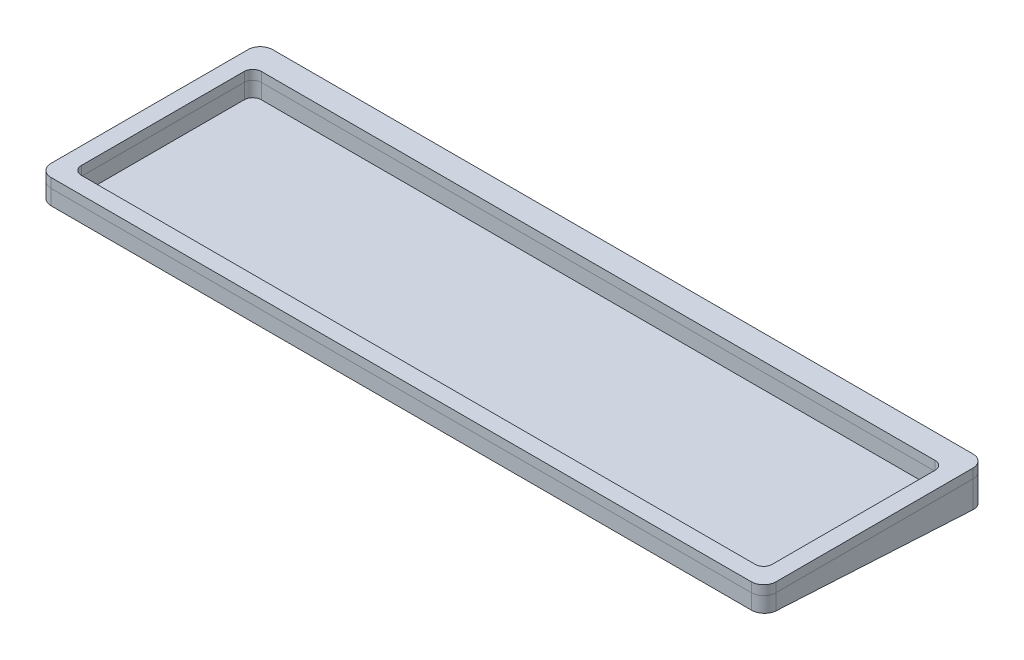
SolidWorks part; units mm, degrees
ref_plane "Front Plane" through (0, 0, 0) normal (0, 0, 1) x (1, 0, 0)
ref_plane "Top Plane" through (0, 0, 0) normal (0, 1, 0) x (1, 0, 0)
ref_plane "Right Plane" through (0, 0, 0) normal (1, 0, 0) x (0, 0, -1)
sketch "Sketch1" plane through (0, 0, 0) normal (0, 1, 0) x (1, 0, 0)
  line L0 (-179.825, 47.6224) -> (-179.825, 47.625)
  line L1 (-179.8217, 47.625) -> (179.825, 47.625)
  line L2 (-179.825, 47.6224) -> (-179.825, -47.625)
  line L3 (-179.825, -47.625) -> (179.825, -47.625)
  line L4 (179.825, 47.625) -> (179.825, -47.625)
  line L5 (-179.825, 47.625) -> (179.825, -47.625) construction
  line L6 (-179.825, -47.625) -> (179.825, 47.625) construction
  line L7 (-179.825, 47.625) -> (-179.8217, 47.625)
  circle A4 centre (157.075, 19.175) radius 1.1
  circle A5 centre (136.925, -16.775) radius 1.1
  circle A6 centre (-153.475, 33.725) radius 1.1
  circle A7 centre (17.925, 22.275) radius 1.1
  circle A8 centre (17.875, -35.075) radius 1.1
  circle A9 centre (-130.375, -35.725) radius 1.1
  point P0 (0, 0)
  dimension "D4" = 2.2
  dimension "D7" = 2.2
  dimension "D8" = 2.2
  dimension "D9" = 2.2
  dimension "D10" = 2.2
  dimension "D11" = 2.2
  dimension "D1" = 359.65
  dimension "D2" = 95.25
  dimension "D5" = 22.75
  dimension "D6" = 28.45
  dimension "D12" = 42.9
  dimension "D13" = 30.85
  dimension "D14" = 25.35
  dimension "D15" = 161.9
  dimension "D16" = 12.55
  dimension "D17" = 161.95
  dimension "D18" = 11.9
  dimension "D19" = 49.45
  dimension "D20" = 13.9
  dimension "D21" = 26.35
sketch "Sketch2" plane through (0, 0, 0) normal (0, 1, 0) x (1, 0, 0)
  line L0 (-188.825, 54.625) -> (-188.825, 60.625)
  line L1 (-188.825, 60.625) -> (-182.825, 60.625)
  line L3 (-188.825, 60.625) -> (-191.825, 60.625)
  line L4 (-182.825, 46.625) -> (-182.825, -46.625)
  line L5 (-178.825, -47.625) -> (178.825, -47.625)
  line L6 (182.825, 46.625) -> (182.825, -46.625)
  line L7 (-178.825, 47.625) -> (178.825, 47.625)
  line L8 (-182.825, 46.625) -> (-182.825, 47.625)
  line L9 (-182.825, 60.625) -> (188.825, 60.625)
  line L10 (-188.825, 54.625) -> (-188.825, -56.625)
  line L11 (-188.825, -56.625) -> (188.825, -56.625)
  line L12 (188.825, 60.625) -> (188.825, -56.625)
  line L13 (-182.825, 47.625) -> (-178.825, 47.625)
  line L14 (-182.825, -46.625) -> (-182.825, -47.625)
  line L15 (-182.825, -47.625) -> (-178.825, -47.625)
  line L16 (178.825, -47.625) -> (182.825, -47.625)
  line L17 (182.825, -47.625) -> (182.825, -46.625)
  line L18 (178.825, 47.625) -> (182.825, 47.625)
  line L19 (182.825, 47.625) -> (182.825, 46.625)
  line L20 (-188.825, 60.625) -> (-188.825, -56.625)
  line L21 (-188.825, -56.625) -> (-191.825, -56.625)
  line L22 (-191.825, 60.625) -> (-191.825, -56.625)
  line L23 (188.825, 60.625) -> (191.825, 60.625)
  line L24 (188.825, 60.625) -> (188.825, -56.625)
  line L25 (188.825, -56.625) -> (191.825, -56.625)
  line L26 (191.825, 60.625) -> (191.825, -56.625)
  circle A0 centre (157.075, 19.175) radius 1.1 construction
  circle A1 centre (136.925, -16.775) radius 1.1 construction
  circle A2 centre (17.875, -35.075) radius 1.1 construction
  circle A3 centre (17.925, 22.275) radius 1.1 construction
  circle A4 centre (-153.475, 33.725) radius 1.1 construction
  circle A5 centre (-130.375, -35.725) radius 1.1 construction
  circle A10 centre (157.075, 19.175) radius 1.1
  circle A11 centre (136.925, -16.775) radius 1.1
  circle A12 centre (17.875, -35.075) radius 1.1
  circle A13 centre (17.925, 22.275) radius 1.1
  circle A14 centre (-153.475, 33.725) radius 1.1
  circle A15 centre (-130.375, -35.725) radius 1.1
  point P30 (0, 0)
  dimension "D5" = 3
  dimension "D6" = 3
  dimension "D1" = 13
  dimension "D2" = 9
  dimension "D3" = 6
  dimension "D4" = 6
extrude "Boss-Extrude1" add sketch "Sketch2" along normal blind 13 contours L10 L11 L12 L9 L18 L19 L6 L17 L16 L5 L15 L14 L4 L8 L13 L7 | L20 L3 L22 L21 | L24 L23 L26 L25 region at (-184.8707, 0, -57.625)
sketch "Sketch4" plane through (0, 0, 0) normal (0, -1, 0) x (1, 0, 0)
  line L1 (-191.825, -60.625) -> (191.825, -60.625) construction
  line L3 (-191.825, 56.625) -> (191.825, 56.625) construction
  line L4 (-182.825, 47.625) -> (-182.825, -47.625)
  line L5 (182.825, 47.625) -> (-182.825, 47.625)
  line L6 (182.825, -47.625) -> (182.825, 47.625)
  line L7 (-182.825, -47.625) -> (182.825, -47.625)
  line L8 (-182.825, 47.625) -> (-182.825, -47.625)
  line L10 (182.825, -47.625) -> (182.825, 47.625)
  line L11 (-182.825, -47.625) -> (182.825, -47.625)
  line L12 (191.825, -60.625) -> (191.825, 56.625)
  line L13 (-191.825, -60.625) -> (191.825, -60.625)
  line L14 (-191.825, -60.625) -> (-191.825, 56.625)
  line L15 (-191.825, 56.625) -> (191.825, 56.625)
  line M10 (-182.825, -47.625) -> (-182.825, 47.625)
  line M12 (-182.825, 47.625) -> (182.825, 47.625)
  line M14 (182.825, 47.625) -> (182.825, -47.625)
  line M16 (182.825, -47.625) -> (-182.825, -47.625)
  line M19 (-191.825, -60.625) -> (191.825, -60.625)
  line M23 (191.825, 56.625) -> (-191.825, 56.625)
  dimension "D1" = 0
extrude "Boss-Extrude3" add sketch "Sketch4" along normal blind 10.5 contours M19 M23 M16 M10 M12 M14 | M16 M14 M12 M10 region at (0, 0, 0) region at (0, 0, -56.6133)
sketch "Sketch11" plane through (-191.825, 0, 0) normal (-1, 0, 0) x (0, 0, 1)
  line L0 (-60.625, 0) -> (56.625, 0) construction
  line L1 (-60.625, 13) -> (-60.625, -10.5) construction
  line L2 (56.625, 13) -> (56.625, -10.5) construction
  line L3 (56.625, -10.5) -> (-60.625, -10.5) construction
  line L4 (-60.625, -10.5) -> (-60.625, -6.5)
  line L5 (-60.625, -6.5) -> (56.625, 0)
  line L6 (56.625, 0) -> (56.625, -10.5)
  line L7 (56.625, -10.5) -> (-60.625, -10.5)
  dimension "D1" = 10.5
  dimension "D2" = 4
extrude "Cut-Extrude1" cut sketch "Sketch11" against normal blind 400
sketch "Sketch9" plane through (0, 0, 0) normal (0, 1, 0) x (1, 0, 0)
  line L0 (-121.9453, 45.1) -> (-108.9453, 45.1)
  line L1 (-121.9453, 31.1) -> (-108.9453, 31.1)
  line L2 (-122.4453, 44.6) -> (-122.4453, 31.6)
  line L3 (-108.4453, 44.6) -> (-108.4453, 31.6)
  line L4 (-102.8953, 45.1) -> (-89.8953, 45.1)
  line L5 (-102.8953, 31.1) -> (-89.8953, 31.1)
  line L6 (-103.3953, 44.6) -> (-103.3953, 31.6)
  line L7 (-89.3953, 44.6) -> (-89.3953, 31.6)
  line L8 (-83.8453, 45.1) -> (-70.8453, 45.1)
  line L9 (-83.8453, 31.1) -> (-70.8453, 31.1)
  line L10 (-84.3453, 44.6) -> (-84.3453, 31.6)
  line L11 (-70.3453, 44.6) -> (-70.3453, 31.6)
  line L12 (-64.7953, 45.1) -> (-51.7953, 45.1)
  line L13 (-64.7953, 31.1) -> (-51.7953, 31.1)
  line L14 (-65.2953, 44.6) -> (-65.2953, 31.6)
  line L15 (-51.2953, 44.6) -> (-51.2953, 31.6)
  line L16 (-45.7453, 45.1) -> (-32.7453, 45.1)
  line L17 (-45.7453, 31.1) -> (-32.7453, 31.1)
  line L18 (-46.2453, 44.6) -> (-46.2453, 31.6)
  line L19 (-32.2453, 44.6) -> (-32.2453, 31.6)
  line L20 (-26.6953, 45.1) -> (-13.6953, 45.1)
  line L21 (-26.6953, 31.1) -> (-13.6953, 31.1)
  line L22 (-27.1953, 44.6) -> (-27.1953, 31.6)
  line L23 (-13.1953, 44.6) -> (-13.1953, 31.6)
  line L24 (-7.6453, 45.1) -> (5.3547, 45.1)
  line L25 (-7.6453, 31.1) -> (5.3547, 31.1)
  line L26 (-8.1453, 44.6) -> (-8.1453, 31.6)
  line L27 (5.8547, 44.6) -> (5.8547, 31.6)
  line L28 (11.4047, 45.1) -> (24.4047, 45.1)
  line L29 (11.4047, 31.1) -> (24.4047, 31.1)
  line L30 (10.9047, 44.6) -> (10.9047, 31.6)
  line L31 (24.9047, 44.6) -> (24.9047, 31.6)
  line L32 (30.4547, 45.1) -> (43.4547, 45.1)
  line L33 (30.4547, 31.1) -> (43.4547, 31.1)
  line L34 (29.9547, 44.6) -> (29.9547, 31.6)
  line L35 (43.9547, 44.6) -> (43.9547, 31.6)
  line L36 (49.5047, 45.1) -> (62.5047, 45.1)
  line L37 (49.5047, 31.1) -> (62.5047, 31.1)
  line L38 (49.0047, 44.6) -> (49.0047, 31.6)
  line L39 (63.0047, 44.6) -> (63.0047, 31.6)
  line L40 (68.5547, 45.1) -> (81.5547, 45.1)
  line L41 (68.5547, 31.1) -> (81.5547, 31.1)
  line L42 (68.0547, 44.6) -> (68.0547, 31.6)
  line L43 (82.0547, 44.6) -> (82.0547, 31.6)
  line L44 (87.6047, 45.1) -> (100.6047, 45.1)
  line L45 (87.6047, 31.1) -> (100.6047, 31.1)
  line L46 (87.1047, 44.6) -> (87.1047, 31.6)
  line L47 (101.1047, 44.6) -> (101.1047, 31.6)
  line L48 (106.6547, 45.1) -> (119.6547, 45.1)
  line L49 (106.6547, 31.1) -> (119.6547, 31.1)
  line L50 (106.1547, 44.6) -> (106.1547, 31.6)
  line L51 (120.1547, 44.6) -> (120.1547, 31.6)
  line L52 (135.2297, 45.1) -> (148.2297, 45.1)
  line L53 (135.2297, 31.1) -> (148.2297, 31.1)
  line L54 (134.7297, 44.6) -> (134.7297, 31.6)
  line L55 (148.7297, 44.6) -> (148.7297, 31.6)
  line L56 (150.6677, 44.1) -> (156.6677, 44.1)
  line L57 (150.6677, 29.1) -> (156.6677, 29.1)
  line L58 (150.1677, 43.6) -> (150.1677, 29.6)
  line L59 (157.1677, 43.6) -> (157.1677, 29.6)
  line L60 (126.7917, 44.1) -> (132.7917, 44.1)
  line L61 (126.7917, 29.1) -> (132.7917, 29.1)
  line L62 (126.2917, 43.6) -> (126.2917, 29.6)
  line L63 (133.2917, 43.6) -> (133.2917, 29.6)
  line L64 (163.8047, 45.1) -> (176.8047, 45.1)
  line L65 (163.8047, 31.1) -> (176.8047, 31.1)
  line L66 (163.3047, 44.6) -> (163.3047, 31.6)
  line L67 (177.3047, 44.6) -> (177.3047, 31.6)
  line L68 (-117.1828, 26.05) -> (-104.1828, 26.05)
  line L69 (-117.1828, 12.05) -> (-104.1828, 12.05)
  line L70 (-117.6828, 25.55) -> (-117.6828, 12.55)
  line L71 (-103.6828, 25.55) -> (-103.6828, 12.55)
  line L72 (-93.3703, 26.05) -> (-80.3703, 26.05)
  line L73 (-93.3703, 12.05) -> (-80.3703, 12.05)
  line L74 (-93.8703, 25.55) -> (-93.8703, 12.55)
  line L75 (-79.8703, 25.55) -> (-79.8703, 12.55)
  line L76 (-74.3203, 26.05) -> (-61.3203, 26.05)
  line L77 (-74.3203, 12.05) -> (-61.3203, 12.05)
  line L78 (-74.8203, 25.55) -> (-74.8203, 12.55)
  line L79 (-60.8203, 25.55) -> (-60.8203, 12.55)
  line L80 (-55.2703, 26.05) -> (-42.2703, 26.05)
  line L81 (-55.2703, 12.05) -> (-42.2703, 12.05)
  line L82 (-55.7703, 25.55) -> (-55.7703, 12.55)
  line L83 (-41.7703, 25.55) -> (-41.7703, 12.55)
  line L84 (-36.2203, 26.05) -> (-23.2203, 26.05)
  line L85 (-36.2203, 12.05) -> (-23.2203, 12.05)
  line L86 (-36.7203, 25.55) -> (-36.7203, 12.55)
  line L87 (-22.7203, 25.55) -> (-22.7203, 12.55)
  line L88 (-17.1703, 26.05) -> (-4.1703, 26.05)
  line L89 (-17.1703, 12.05) -> (-4.1703, 12.05)
  line L90 (-17.6703, 25.55) -> (-17.6703, 12.55)
  line L91 (-3.6703, 25.55) -> (-3.6703, 12.55)
  line L92 (1.8797, 26.05) -> (14.8797, 26.05)
  line L93 (1.8797, 12.05) -> (14.8797, 12.05)
  line L94 (1.3797, 25.55) -> (1.3797, 12.55)
  line L95 (15.3797, 25.55) -> (15.3797, 12.55)
  line L96 (20.9297, 26.05) -> (33.9297, 26.05)
  line L97 (20.9297, 12.05) -> (33.9297, 12.05)
  line L98 (20.4297, 25.55) -> (20.4297, 12.55)
  line L99 (34.4297, 25.55) -> (34.4297, 12.55)
  line L100 (39.9797, 26.05) -> (52.9797, 26.05)
  line L101 (39.9797, 12.05) -> (52.9797, 12.05)
  line L102 (39.4797, 25.55) -> (39.4797, 12.55)
  line L103 (53.4797, 25.55) -> (53.4797, 12.55)
  line L104 (59.0297, 26.05) -> (72.0297, 26.05)
  line L105 (59.0297, 12.05) -> (72.0297, 12.05)
  line L106 (58.5297, 25.55) -> (58.5297, 12.55)
  line L107 (72.5297, 25.55) -> (72.5297, 12.55)
  line L108 (78.0797, 26.05) -> (91.0797, 26.05)
  line L109 (78.0797, 12.05) -> (91.0797, 12.05)
  line L110 (77.5797, 25.55) -> (77.5797, 12.55)
  line L111 (91.5797, 25.55) -> (91.5797, 12.55)
  line L112 (97.1297, 26.05) -> (110.1297, 26.05)
  line L113 (97.1297, 12.05) -> (110.1297, 12.05)
  line L114 (96.6297, 25.55) -> (96.6297, 12.55)
  line L115 (110.6297, 25.55) -> (110.6297, 12.55)
  line L116 (116.1797, 26.05) -> (129.1797, 26.05)
  line L117 (116.1797, 12.05) -> (129.1797, 12.05)
  line L118 (115.6797, 25.55) -> (115.6797, 12.55)
  line L119 (129.6797, 25.55) -> (129.6797, 12.55)
  line L120 (139.9922, 26.05) -> (152.9922, 26.05)
  line L121 (139.9922, 12.05) -> (152.9922, 12.05)
  line L122 (139.4922, 25.55) -> (139.4922, 12.55)
  line L123 (153.4922, 25.55) -> (153.4922, 12.55)
  line L124 (163.8047, 26.05) -> (176.8047, 26.05)
  line L125 (163.8047, 12.05) -> (176.8047, 12.05)
  line L126 (163.3047, 25.55) -> (163.3047, 12.55)
  line L127 (177.3047, 25.55) -> (177.3047, 12.55)
  line L128 (-114.8016, 7) -> (-101.8016, 7)
  line L129 (-114.8016, -7) -> (-101.8016, -7)
  line L130 (-115.3016, 6.5) -> (-115.3016, -6.5)
  line L131 (-101.3016, 6.5) -> (-101.3016, -6.5)
  line L132 (-88.6078, 7) -> (-75.6078, 7)
  line L133 (-88.6078, -7) -> (-75.6078, -7)
  line L134 (-89.1078, 6.5) -> (-89.1078, -6.5)
  line L135 (-75.1078, 6.5) -> (-75.1078, -6.5)
  line L136 (-69.5578, 7) -> (-56.5578, 7)
  line L137 (-69.5578, -7) -> (-56.5578, -7)
  line L138 (-70.0578, 6.5) -> (-70.0578, -6.5)
  line L139 (-56.0578, 6.5) -> (-56.0578, -6.5)
  line L140 (-50.5078, 7) -> (-37.5078, 7)
  line L141 (-50.5078, -7) -> (-37.5078, -7)
  line L142 (-51.0078, 6.5) -> (-51.0078, -6.5)
  line L143 (-37.0078, 6.5) -> (-37.0078, -6.5)
  line L144 (-31.4578, 7) -> (-18.4578, 7)
  line L145 (-31.4578, -7) -> (-18.4578, -7)
  line L146 (-31.9578, 6.5) -> (-31.9578, -6.5)
  line L147 (-17.9578, 6.5) -> (-17.9578, -6.5)
  line L148 (-12.4078, 7) -> (0.5922, 7)
  line L149 (-12.4078, -7) -> (0.5922, -7)
  line L150 (-12.9078, 6.5) -> (-12.9078, -6.5)
  line L151 (1.0922, 6.5) -> (1.0922, -6.5)
  line L152 (6.6422, 7) -> (19.6422, 7)
  line L153 (6.6422, -7) -> (19.6422, -7)
  line L154 (6.1422, 6.5) -> (6.1422, -6.5)
  line L155 (20.1422, 6.5) -> (20.1422, -6.5)
  line L156 (25.6922, 7) -> (38.6922, 7)
  line L157 (25.6922, -7) -> (38.6922, -7)
  line L158 (25.1922, 6.5) -> (25.1922, -6.5)
  line L159 (39.1922, 6.5) -> (39.1922, -6.5)
  line L160 (44.7422, 7) -> (57.7422, 7)
  line L161 (44.7422, -7) -> (57.7422, -7)
  line L162 (44.2422, 6.5) -> (44.2422, -6.5)
  line L163 (58.2422, 6.5) -> (58.2422, -6.5)
  line L164 (63.7922, 7) -> (76.7922, 7)
  line L165 (63.7922, -7) -> (76.7922, -7)
  line L166 (63.2922, 6.5) -> (63.2922, -6.5)
  line L167 (77.2922, 6.5) -> (77.2922, -6.5)
  line L168 (82.8422, 7) -> (95.8422, 7)
  line L169 (82.8422, -7) -> (95.8422, -7)
  line L170 (82.3422, 6.5) -> (82.3422, -6.5)
  line L171 (96.3422, 6.5) -> (96.3422, -6.5)
  line L172 (101.8922, 7) -> (114.8922, 7)
  line L173 (101.8922, -7) -> (114.8922, -7)
  line L174 (101.3922, 6.5) -> (101.3922, -6.5)
  line L175 (115.3922, 6.5) -> (115.3922, -6.5)
  line L176 (132.8484, 7) -> (145.8484, 7)
  line L177 (132.8484, -7) -> (145.8484, -7)
  line L178 (132.3484, 6.5) -> (132.3484, -6.5)
  line L179 (146.3484, 6.5) -> (146.3484, -6.5)
  line L180 (148.2864, 6) -> (154.2864, 6)
  line L181 (148.2864, -9) -> (154.2864, -9)
  line L182 (147.7864, 5.5) -> (147.7864, -8.5)
  line L183 (154.7864, 5.5) -> (154.7864, -8.5)
  line L184 (124.4104, 6) -> (130.4104, 6)
  line L185 (124.4104, -9) -> (130.4104, -9)
  line L186 (123.9104, 5.5) -> (123.9104, -8.5)
  line L187 (130.9104, 5.5) -> (130.9104, -8.5)
  line L188 (163.8047, 7) -> (176.8047, 7)
  line L189 (163.8047, -7) -> (176.8047, -7)
  line L190 (163.3047, 6.5) -> (163.3047, -6.5)
  line L191 (177.3047, 6.5) -> (177.3047, -6.5)
  line L192 (-110.0391, -12.05) -> (-97.0391, -12.05)
  line L193 (-110.0391, -26.05) -> (-97.0391, -26.05)
  line L194 (-110.5391, -12.55) -> (-110.5391, -25.55)
  line L195 (-96.5391, -12.55) -> (-96.5391, -25.55)
  line L196 (-94.6011, -13.05) -> (-88.6011, -13.05)
  line L197 (-94.6011, -28.05) -> (-88.6011, -28.05)
  line L198 (-95.1011, -13.55) -> (-95.1011, -27.55)
  line L199 (-88.1011, -13.55) -> (-88.1011, -27.55)
  line L200 (-118.4771, -13.05) -> (-112.4771, -13.05)
  line L201 (-118.4771, -28.05) -> (-112.4771, -28.05)
  line L202 (-118.9771, -13.55) -> (-118.9771, -27.55)
  line L203 (-111.9771, -13.55) -> (-111.9771, -27.55)
  line L204 (-79.0828, -12.05) -> (-66.0828, -12.05)
  line L205 (-79.0828, -26.05) -> (-66.0828, -26.05)
  line L206 (-79.5828, -12.55) -> (-79.5828, -25.55)
  line L207 (-65.5828, -12.55) -> (-65.5828, -25.55)
  line L208 (-60.0328, -12.05) -> (-47.0328, -12.05)
  line L209 (-60.0328, -26.05) -> (-47.0328, -26.05)
  line L210 (-60.5328, -12.55) -> (-60.5328, -25.55)
  line L211 (-46.5328, -12.55) -> (-46.5328, -25.55)
  line L212 (-40.9828, -12.05) -> (-27.9828, -12.05)
  line L213 (-40.9828, -26.05) -> (-27.9828, -26.05)
  line L214 (-41.4828, -12.55) -> (-41.4828, -25.55)
  line L215 (-27.4828, -12.55) -> (-27.4828, -25.55)
  line L216 (-21.9328, -12.05) -> (-8.9328, -12.05)
  line L217 (-21.9328, -26.05) -> (-8.9328, -26.05)
  line L218 (-22.4328, -12.55) -> (-22.4328, -25.55)
  line L219 (-8.4328, -12.55) -> (-8.4328, -25.55)
  line L220 (-2.8828, -12.05) -> (10.1172, -12.05)
  line L221 (-2.8828, -26.05) -> (10.1172, -26.05)
  line L222 (-3.3828, -12.55) -> (-3.3828, -25.55)
  line L223 (10.6172, -12.55) -> (10.6172, -25.55)
  line L224 (16.1672, -12.05) -> (29.1672, -12.05)
  line L225 (16.1672, -26.05) -> (29.1672, -26.05)
  line L226 (15.6672, -12.55) -> (15.6672, -25.55)
  line L227 (29.6672, -12.55) -> (29.6672, -25.55)
  line L228 (35.2172, -12.05) -> (48.2172, -12.05)
  line L229 (35.2172, -26.05) -> (48.2172, -26.05)
  line L230 (34.7172, -12.55) -> (34.7172, -25.55)
  line L231 (48.7172, -12.55) -> (48.7172, -25.55)
  line L232 (54.2672, -12.05) -> (67.2672, -12.05)
  line L233 (54.2672, -26.05) -> (67.2672, -26.05)
  line L234 (53.7672, -12.55) -> (53.7672, -25.55)
  line L235 (67.7672, -12.55) -> (67.7672, -25.55)
  line L236 (73.3172, -12.05) -> (86.3172, -12.05)
  line L237 (73.3172, -26.05) -> (86.3172, -26.05)
  line L238 (72.8172, -12.55) -> (72.8172, -25.55)
  line L239 (86.8172, -12.55) -> (86.8172, -25.55)
  line L240 (92.3672, -12.05) -> (105.3672, -12.05)
  line L241 (92.3672, -26.05) -> (105.3672, -26.05)
  line L242 (91.8672, -12.55) -> (91.8672, -25.55)
  line L243 (105.8672, -12.55) -> (105.8672, -25.55)
  line L244 (118.5609, -12.05) -> (131.5609, -12.05)
  line L245 (118.5609, -26.05) -> (131.5609, -26.05)
  line L246 (118.0609, -12.55) -> (118.0609, -25.55)
  line L247 (132.0609, -12.55) -> (132.0609, -25.55)
  line L248 (144.7547, -12.05) -> (157.7547, -12.05)
  line L249 (144.7547, -26.05) -> (157.7547, -26.05)
  line L250 (144.2547, -12.55) -> (144.2547, -25.55)
  line L251 (158.2547, -12.55) -> (158.2547, -25.55)
  line L252 (163.8047, -12.05) -> (176.8047, -12.05)
  line L253 (163.8047, -26.05) -> (176.8047, -26.05)
  line L254 (163.3047, -12.55) -> (163.3047, -25.55)
  line L255 (177.3047, -12.55) -> (177.3047, -25.55)
  line L256 (-119.5641, -31.1) -> (-106.5641, -31.1)
  line L257 (-119.5641, -45.1) -> (-106.5641, -45.1)
  line L258 (-120.0641, -31.6) -> (-120.0641, -44.6)
  line L259 (-106.0641, -31.6) -> (-106.0641, -44.6)
  line L260 (-95.7516, -31.1) -> (-82.7516, -31.1)
  line L261 (-95.7516, -45.1) -> (-82.7516, -45.1)
  line L262 (-96.2516, -31.6) -> (-96.2516, -44.6)
  line L263 (-82.2516, -31.6) -> (-82.2516, -44.6)
  line L264 (-71.9391, -31.1) -> (-58.9391, -31.1)
  line L265 (-71.9391, -45.1) -> (-58.9391, -45.1)
  line L266 (-72.4391, -31.6) -> (-72.4391, -44.6)
  line L267 (-58.4391, -31.6) -> (-58.4391, -44.6)
  line L268 (-0.5016, -31.1) -> (12.4984, -31.1)
  line L269 (-0.5016, -45.1) -> (12.4984, -45.1)
  line L270 (-1.0016, -31.6) -> (-1.0016, -44.6)
  line L271 (12.9984, -31.6) -> (12.9984, -44.6)
  line L272 (52.9984, -32.1) -> (58.9984, -32.1)
  line L273 (52.9984, -47.1) -> (58.9984, -47.1)
  line L274 (52.4984, -32.6) -> (52.4984, -46.6)
  line L275 (59.4984, -32.6) -> (59.4984, -46.6)
  line L276 (-47.0016, -32.1) -> (-41.0016, -32.1)
  line L277 (-47.0016, -47.1) -> (-41.0016, -47.1)
  line L278 (-47.5016, -32.6) -> (-47.5016, -46.6)
  line L279 (-40.5016, -32.6) -> (-40.5016, -46.6)
  line L280 (68.5547, -31.1) -> (81.5547, -31.1)
  line L281 (68.5547, -45.1) -> (81.5547, -45.1)
  line L282 (68.0547, -31.6) -> (68.0547, -44.6)
  line L283 (82.0547, -31.6) -> (82.0547, -44.6)
  line L284 (87.6047, -31.1) -> (100.6047, -31.1)
  line L285 (87.6047, -45.1) -> (100.6047, -45.1)
  line L286 (87.1047, -31.6) -> (87.1047, -44.6)
  line L287 (101.1047, -31.6) -> (101.1047, -44.6)
  line L288 (106.6547, -31.1) -> (119.6547, -31.1)
  line L289 (106.6547, -45.1) -> (119.6547, -45.1)
  line L290 (106.1547, -31.6) -> (106.1547, -44.6)
  line L291 (120.1547, -31.6) -> (120.1547, -44.6)
  line L292 (125.7047, -31.1) -> (138.7047, -31.1)
  line L293 (125.7047, -45.1) -> (138.7047, -45.1)
  line L294 (125.2047, -31.6) -> (125.2047, -44.6)
  line L295 (139.2047, -31.6) -> (139.2047, -44.6)
  line L296 (144.7547, -31.1) -> (157.7547, -31.1)
  line L297 (144.7547, -45.1) -> (157.7547, -45.1)
  line L298 (144.2547, -31.6) -> (144.2547, -44.6)
  line L299 (158.2547, -31.6) -> (158.2547, -44.6)
  line L300 (163.8047, -31.1) -> (176.8047, -31.1)
  line L301 (163.8047, -45.1) -> (176.8047, -45.1)
  line L302 (163.3047, -31.6) -> (163.3047, -44.6)
  line L303 (177.3047, -31.6) -> (177.3047, -44.6)
  line L304 (-122.9703, 47.625) -> (-103.2456, 47.625)
  line L305 (-122.9703, -47.625) -> (-103.2456, -47.625)
  line L306 (-124.9703, 45.625) -> (-124.9703, -45.625)
  line L307 (179.8297, 45.625) -> (179.8297, 7.5)
  line L308 (-103.2456, 53.125) -> (-103.2456, 47.625)
  line L309 (-124.9703, 47.625) -> (-103.2456, 47.625)
  line L311 (-101.2456, 55.125) -> (-90.2456, 55.125)
  line L312 (-88.2456, 47.625) -> (-88.2456, 53.125)
  line L313 (-23.2456, 53.125) -> (-23.2456, 47.625)
  line L314 (-21.2456, 55.125) -> (-10.2456, 55.125)
  line L315 (-8.2456, 47.625) -> (-8.2456, 53.125)
  line L316 (56.7544, 53.125) -> (56.7544, 47.625)
  line L317 (58.7544, 55.125) -> (69.7544, 55.125)
  line L318 (71.7544, 47.625) -> (71.7544, 53.125)
  line L319 (136.7544, 53.125) -> (136.7544, 47.625)
  line L320 (138.7544, 55.125) -> (149.7544, 55.125)
  line L321 (151.7544, 47.625) -> (151.7544, 53.125)
  line L322 (-88.2456, 47.625) -> (-23.2456, 47.625)
  line L323 (-8.2456, 47.625) -> (56.7544, 47.625)
  line L324 (71.7544, 47.625) -> (136.7544, 47.625)
  line L325 (151.7544, 47.625) -> (177.8297, 47.625)
  line L326 (-23.2456, -47.625) -> (-23.2456, -52.625)
  line L327 (-5.699, -47.625) -> (-5.699, -52.625)
  line L329 (-103.2456, -47.625) -> (-103.2456, -52.625)
  line L330 (-101.2456, -54.625) -> (-87.699, -54.625)
  line L331 (-85.699, -47.625) -> (-85.699, -52.625)
  line L332 (-21.2456, -54.625) -> (-7.699, -54.625)
  line L333 (56.7544, -47.625) -> (56.7544, -52.625)
  line L334 (74.301, -47.625) -> (74.301, -52.625)
  line L335 (58.7544, -54.625) -> (72.301, -54.625)
  line L336 (136.7544, -47.625) -> (136.7544, -52.625)
  line L337 (154.301, -47.625) -> (154.301, -52.625)
  line L338 (138.7544, -54.625) -> (152.301, -54.625)
  line L339 (-85.699, -47.625) -> (-23.2456, -47.625)
  line L340 (-5.699, -47.625) -> (56.7544, -47.625)
  line L341 (74.301, -47.625) -> (136.7544, -47.625)
  line L342 (154.301, -47.625) -> (177.8297, -47.625)
  line L343 (179.8297, -7.5) -> (179.8297, -45.625)
  line L348 (179.8297, 7.5) -> (179.8297, -7.5)
  arc A0 (-121.9453, 45.1) -> (-122.4453, 44.6) centre (-121.9453, 44.6) ccw
  arc A1 (-108.4453, 44.6) -> (-108.9453, 45.1) centre (-108.9453, 44.6) ccw
  arc A2 (-122.4453, 31.6) -> (-121.9453, 31.1) centre (-121.9453, 31.6) ccw
  arc A3 (-108.9453, 31.1) -> (-108.4453, 31.6) centre (-108.9453, 31.6) ccw
  arc A4 (-102.8953, 45.1) -> (-103.3953, 44.6) centre (-102.8953, 44.6) ccw
  arc A5 (-89.3953, 44.6) -> (-89.8953, 45.1) centre (-89.8953, 44.6) ccw
  arc A6 (-103.3953, 31.6) -> (-102.8953, 31.1) centre (-102.8953, 31.6) ccw
  arc A7 (-89.8953, 31.1) -> (-89.3953, 31.6) centre (-89.8953, 31.6) ccw
  arc A8 (-83.8453, 45.1) -> (-84.3453, 44.6) centre (-83.8453, 44.6) ccw
  arc A9 (-70.3453, 44.6) -> (-70.8453, 45.1) centre (-70.8453, 44.6) ccw
  arc A10 (-84.3453, 31.6) -> (-83.8453, 31.1) centre (-83.8453, 31.6) ccw
  arc A11 (-70.8453, 31.1) -> (-70.3453, 31.6) centre (-70.8453, 31.6) ccw
  arc A12 (-64.7953, 45.1) -> (-65.2953, 44.6) centre (-64.7953, 44.6) ccw
  arc A13 (-51.2953, 44.6) -> (-51.7953, 45.1) centre (-51.7953, 44.6) ccw
  arc A14 (-65.2953, 31.6) -> (-64.7953, 31.1) centre (-64.7953, 31.6) ccw
  arc A15 (-51.7953, 31.1) -> (-51.2953, 31.6) centre (-51.7953, 31.6) ccw
  arc A16 (-45.7453, 45.1) -> (-46.2453, 44.6) centre (-45.7453, 44.6) ccw
  arc A17 (-32.2453, 44.6) -> (-32.7453, 45.1) centre (-32.7453, 44.6) ccw
  arc A18 (-46.2453, 31.6) -> (-45.7453, 31.1) centre (-45.7453, 31.6) ccw
  arc A19 (-32.7453, 31.1) -> (-32.2453, 31.6) centre (-32.7453, 31.6) ccw
  arc A20 (-26.6953, 45.1) -> (-27.1953, 44.6) centre (-26.6953, 44.6) ccw
  arc A21 (-13.1953, 44.6) -> (-13.6953, 45.1) centre (-13.6953, 44.6) ccw
  arc A22 (-27.1953, 31.6) -> (-26.6953, 31.1) centre (-26.6953, 31.6) ccw
  arc A23 (-13.6953, 31.1) -> (-13.1953, 31.6) centre (-13.6953, 31.6) ccw
  arc A24 (-7.6453, 45.1) -> (-8.1453, 44.6) centre (-7.6453, 44.6) ccw
  arc A25 (5.8547, 44.6) -> (5.3547, 45.1) centre (5.3547, 44.6) ccw
  arc A26 (-8.1453, 31.6) -> (-7.6453, 31.1) centre (-7.6453, 31.6) ccw
  arc A27 (5.3547, 31.1) -> (5.8547, 31.6) centre (5.3547, 31.6) ccw
  arc A28 (11.4047, 45.1) -> (10.9047, 44.6) centre (11.4047, 44.6) ccw
  arc A29 (24.9047, 44.6) -> (24.4047, 45.1) centre (24.4047, 44.6) ccw
  arc A30 (10.9047, 31.6) -> (11.4047, 31.1) centre (11.4047, 31.6) ccw
  arc A31 (24.4047, 31.1) -> (24.9047, 31.6) centre (24.4047, 31.6) ccw
  arc A32 (30.4547, 45.1) -> (29.9547, 44.6) centre (30.4547, 44.6) ccw
  arc A33 (43.9547, 44.6) -> (43.4547, 45.1) centre (43.4547, 44.6) ccw
  arc A34 (29.9547, 31.6) -> (30.4547, 31.1) centre (30.4547, 31.6) ccw
  arc A35 (43.4547, 31.1) -> (43.9547, 31.6) centre (43.4547, 31.6) ccw
  arc A36 (49.5047, 45.1) -> (49.0047, 44.6) centre (49.5047, 44.6) ccw
  arc A37 (63.0047, 44.6) -> (62.5047, 45.1) centre (62.5047, 44.6) ccw
  arc A38 (49.0047, 31.6) -> (49.5047, 31.1) centre (49.5047, 31.6) ccw
  arc A39 (62.5047, 31.1) -> (63.0047, 31.6) centre (62.5047, 31.6) ccw
  arc A40 (68.5547, 45.1) -> (68.0547, 44.6) centre (68.5547, 44.6) ccw
  arc A41 (82.0547, 44.6) -> (81.5547, 45.1) centre (81.5547, 44.6) ccw
  arc A42 (68.0547, 31.6) -> (68.5547, 31.1) centre (68.5547, 31.6) ccw
  arc A43 (81.5547, 31.1) -> (82.0547, 31.6) centre (81.5547, 31.6) ccw
  arc A44 (87.6047, 45.1) -> (87.1047, 44.6) centre (87.6047, 44.6) ccw
  arc A45 (101.1047, 44.6) -> (100.6047, 45.1) centre (100.6047, 44.6) ccw
  arc A46 (87.1047, 31.6) -> (87.6047, 31.1) centre (87.6047, 31.6) ccw
  arc A47 (100.6047, 31.1) -> (101.1047, 31.6) centre (100.6047, 31.6) ccw
  arc A48 (106.6547, 45.1) -> (106.1547, 44.6) centre (106.6547, 44.6) ccw
  arc A49 (120.1547, 44.6) -> (119.6547, 45.1) centre (119.6547, 44.6) ccw
  arc A50 (106.1547, 31.6) -> (106.6547, 31.1) centre (106.6547, 31.6) ccw
  arc A51 (119.6547, 31.1) -> (120.1547, 31.6) centre (119.6547, 31.6) ccw
  arc A52 (135.2297, 45.1) -> (134.7297, 44.6) centre (135.2297, 44.6) ccw
  arc A53 (148.7297, 44.6) -> (148.2297, 45.1) centre (148.2297, 44.6) ccw
  arc A54 (134.7297, 31.6) -> (135.2297, 31.1) centre (135.2297, 31.6) ccw
  arc A55 (148.2297, 31.1) -> (148.7297, 31.6) centre (148.2297, 31.6) ccw
  arc A56 (150.6677, 44.1) -> (150.1677, 43.6) centre (150.6677, 43.6) ccw
  arc A57 (157.1677, 43.6) -> (156.6677, 44.1) centre (156.6677, 43.6) ccw
  arc A58 (150.1677, 29.6) -> (150.6677, 29.1) centre (150.6677, 29.6) ccw
  arc A59 (156.6677, 29.1) -> (157.1677, 29.6) centre (156.6677, 29.6) ccw
  arc A60 (126.7917, 44.1) -> (126.2917, 43.6) centre (126.7917, 43.6) ccw
  arc A61 (133.2917, 43.6) -> (132.7917, 44.1) centre (132.7917, 43.6) ccw
  arc A62 (126.2917, 29.6) -> (126.7917, 29.1) centre (126.7917, 29.6) ccw
  arc A63 (132.7917, 29.1) -> (133.2917, 29.6) centre (132.7917, 29.6) ccw
  arc A64 (163.8047, 45.1) -> (163.3047, 44.6) centre (163.8047, 44.6) ccw
  arc A65 (177.3047, 44.6) -> (176.8047, 45.1) centre (176.8047, 44.6) ccw
  arc A66 (163.3047, 31.6) -> (163.8047, 31.1) centre (163.8047, 31.6) ccw
  arc A67 (176.8047, 31.1) -> (177.3047, 31.6) centre (176.8047, 31.6) ccw
  arc A68 (-117.1828, 26.05) -> (-117.6828, 25.55) centre (-117.1828, 25.55) ccw
  arc A69 (-103.6828, 25.55) -> (-104.1828, 26.05) centre (-104.1828, 25.55) ccw
  arc A70 (-117.6828, 12.55) -> (-117.1828, 12.05) centre (-117.1828, 12.55) ccw
  arc A71 (-104.1828, 12.05) -> (-103.6828, 12.55) centre (-104.1828, 12.55) ccw
  arc A72 (-93.3703, 26.05) -> (-93.8703, 25.55) centre (-93.3703, 25.55) ccw
  arc A73 (-79.8703, 25.55) -> (-80.3703, 26.05) centre (-80.3703, 25.55) ccw
  arc A74 (-93.8703, 12.55) -> (-93.3703, 12.05) centre (-93.3703, 12.55) ccw
  arc A75 (-80.3703, 12.05) -> (-79.8703, 12.55) centre (-80.3703, 12.55) ccw
  arc A76 (-74.3203, 26.05) -> (-74.8203, 25.55) centre (-74.3203, 25.55) ccw
  arc A77 (-60.8203, 25.55) -> (-61.3203, 26.05) centre (-61.3203, 25.55) ccw
  arc A78 (-74.8203, 12.55) -> (-74.3203, 12.05) centre (-74.3203, 12.55) ccw
  arc A79 (-61.3203, 12.05) -> (-60.8203, 12.55) centre (-61.3203, 12.55) ccw
  arc A80 (-55.2703, 26.05) -> (-55.7703, 25.55) centre (-55.2703, 25.55) ccw
  arc A81 (-41.7703, 25.55) -> (-42.2703, 26.05) centre (-42.2703, 25.55) ccw
  arc A82 (-55.7703, 12.55) -> (-55.2703, 12.05) centre (-55.2703, 12.55) ccw
  arc A83 (-42.2703, 12.05) -> (-41.7703, 12.55) centre (-42.2703, 12.55) ccw
  arc A84 (-36.2203, 26.05) -> (-36.7203, 25.55) centre (-36.2203, 25.55) ccw
  arc A85 (-22.7203, 25.55) -> (-23.2203, 26.05) centre (-23.2203, 25.55) ccw
  arc A86 (-36.7203, 12.55) -> (-36.2203, 12.05) centre (-36.2203, 12.55) ccw
  arc A87 (-23.2203, 12.05) -> (-22.7203, 12.55) centre (-23.2203, 12.55) ccw
  arc A88 (-17.1703, 26.05) -> (-17.6703, 25.55) centre (-17.1703, 25.55) ccw
  arc A89 (-3.6703, 25.55) -> (-4.1703, 26.05) centre (-4.1703, 25.55) ccw
  arc A90 (-17.6703, 12.55) -> (-17.1703, 12.05) centre (-17.1703, 12.55) ccw
  arc A91 (-4.1703, 12.05) -> (-3.6703, 12.55) centre (-4.1703, 12.55) ccw
  arc A92 (1.8797, 26.05) -> (1.3797, 25.55) centre (1.8797, 25.55) ccw
  arc A93 (15.3797, 25.55) -> (14.8797, 26.05) centre (14.8797, 25.55) ccw
  arc A94 (1.3797, 12.55) -> (1.8797, 12.05) centre (1.8797, 12.55) ccw
  arc A95 (14.8797, 12.05) -> (15.3797, 12.55) centre (14.8797, 12.55) ccw
  arc A96 (20.9297, 26.05) -> (20.4297, 25.55) centre (20.9297, 25.55) ccw
  arc A97 (34.4297, 25.55) -> (33.9297, 26.05) centre (33.9297, 25.55) ccw
  arc A98 (20.4297, 12.55) -> (20.9297, 12.05) centre (20.9297, 12.55) ccw
  arc A99 (33.9297, 12.05) -> (34.4297, 12.55) centre (33.9297, 12.55) ccw
  arc A100 (39.9797, 26.05) -> (39.4797, 25.55) centre (39.9797, 25.55) ccw
  arc A101 (53.4797, 25.55) -> (52.9797, 26.05) centre (52.9797, 25.55) ccw
  arc A102 (39.4797, 12.55) -> (39.9797, 12.05) centre (39.9797, 12.55) ccw
  arc A103 (52.9797, 12.05) -> (53.4797, 12.55) centre (52.9797, 12.55) ccw
  arc A104 (59.0297, 26.05) -> (58.5297, 25.55) centre (59.0297, 25.55) ccw
  arc A105 (72.5297, 25.55) -> (72.0297, 26.05) centre (72.0297, 25.55) ccw
  arc A106 (58.5297, 12.55) -> (59.0297, 12.05) centre (59.0297, 12.55) ccw
  arc A107 (72.0297, 12.05) -> (72.5297, 12.55) centre (72.0297, 12.55) ccw
  arc A108 (78.0797, 26.05) -> (77.5797, 25.55) centre (78.0797, 25.55) ccw
  arc A109 (91.5797, 25.55) -> (91.0797, 26.05) centre (91.0797, 25.55) ccw
  arc A110 (77.5797, 12.55) -> (78.0797, 12.05) centre (78.0797, 12.55) ccw
  arc A111 (91.0797, 12.05) -> (91.5797, 12.55) centre (91.0797, 12.55) ccw
  arc A112 (97.1297, 26.05) -> (96.6297, 25.55) centre (97.1297, 25.55) ccw
  arc A113 (110.6297, 25.55) -> (110.1297, 26.05) centre (110.1297, 25.55) ccw
  arc A114 (96.6297, 12.55) -> (97.1297, 12.05) centre (97.1297, 12.55) ccw
  arc A115 (110.1297, 12.05) -> (110.6297, 12.55) centre (110.1297, 12.55) ccw
  arc A116 (116.1797, 26.05) -> (115.6797, 25.55) centre (116.1797, 25.55) ccw
  arc A117 (129.6797, 25.55) -> (129.1797, 26.05) centre (129.1797, 25.55) ccw
  arc A118 (115.6797, 12.55) -> (116.1797, 12.05) centre (116.1797, 12.55) ccw
  arc A119 (129.1797, 12.05) -> (129.6797, 12.55) centre (129.1797, 12.55) ccw
  arc A120 (139.9922, 26.05) -> (139.4922, 25.55) centre (139.9922, 25.55) ccw
  arc A121 (153.4922, 25.55) -> (152.9922, 26.05) centre (152.9922, 25.55) ccw
  arc A122 (139.4922, 12.55) -> (139.9922, 12.05) centre (139.9922, 12.55) ccw
  arc A123 (152.9922, 12.05) -> (153.4922, 12.55) centre (152.9922, 12.55) ccw
  arc A124 (163.8047, 26.05) -> (163.3047, 25.55) centre (163.8047, 25.55) ccw
  arc A125 (177.3047, 25.55) -> (176.8047, 26.05) centre (176.8047, 25.55) ccw
  arc A126 (163.3047, 12.55) -> (163.8047, 12.05) centre (163.8047, 12.55) ccw
  arc A127 (176.8047, 12.05) -> (177.3047, 12.55) centre (176.8047, 12.55) ccw
  arc A128 (-114.8016, 7) -> (-115.3016, 6.5) centre (-114.8016, 6.5) ccw
  arc A129 (-101.3016, 6.5) -> (-101.8016, 7) centre (-101.8016, 6.5) ccw
  arc A130 (-115.3016, -6.5) -> (-114.8016, -7) centre (-114.8016, -6.5) ccw
  arc A131 (-101.8016, -7) -> (-101.3016, -6.5) centre (-101.8016, -6.5) ccw
  arc A132 (-88.6078, 7) -> (-89.1078, 6.5) centre (-88.6078, 6.5) ccw
  arc A133 (-75.1078, 6.5) -> (-75.6078, 7) centre (-75.6078, 6.5) ccw
  arc A134 (-89.1078, -6.5) -> (-88.6078, -7) centre (-88.6078, -6.5) ccw
  arc A135 (-75.6078, -7) -> (-75.1078, -6.5) centre (-75.6078, -6.5) ccw
  arc A136 (-69.5578, 7) -> (-70.0578, 6.5) centre (-69.5578, 6.5) ccw
  arc A137 (-56.0578, 6.5) -> (-56.5578, 7) centre (-56.5578, 6.5) ccw
  arc A138 (-70.0578, -6.5) -> (-69.5578, -7) centre (-69.5578, -6.5) ccw
  arc A139 (-56.5578, -7) -> (-56.0578, -6.5) centre (-56.5578, -6.5) ccw
  arc A140 (-50.5078, 7) -> (-51.0078, 6.5) centre (-50.5078, 6.5) ccw
  arc A141 (-37.0078, 6.5) -> (-37.5078, 7) centre (-37.5078, 6.5) ccw
  arc A142 (-51.0078, -6.5) -> (-50.5078, -7) centre (-50.5078, -6.5) ccw
  arc A143 (-37.5078, -7) -> (-37.0078, -6.5) centre (-37.5078, -6.5) ccw
  arc A144 (-31.4578, 7) -> (-31.9578, 6.5) centre (-31.4578, 6.5) ccw
  arc A145 (-17.9578, 6.5) -> (-18.4578, 7) centre (-18.4578, 6.5) ccw
  arc A146 (-31.9578, -6.5) -> (-31.4578, -7) centre (-31.4578, -6.5) ccw
  arc A147 (-18.4578, -7) -> (-17.9578, -6.5) centre (-18.4578, -6.5) ccw
  arc A148 (-12.4078, 7) -> (-12.9078, 6.5) centre (-12.4078, 6.5) ccw
  arc A149 (1.0922, 6.5) -> (0.5922, 7) centre (0.5922, 6.5) ccw
  arc A150 (-12.9078, -6.5) -> (-12.4078, -7) centre (-12.4078, -6.5) ccw
  arc A151 (0.5922, -7) -> (1.0922, -6.5) centre (0.5922, -6.5) ccw
  arc A152 (6.6422, 7) -> (6.1422, 6.5) centre (6.6422, 6.5) ccw
  arc A153 (20.1422, 6.5) -> (19.6422, 7) centre (19.6422, 6.5) ccw
  arc A154 (6.1422, -6.5) -> (6.6422, -7) centre (6.6422, -6.5) ccw
  arc A155 (19.6422, -7) -> (20.1422, -6.5) centre (19.6422, -6.5) ccw
  arc A156 (25.6922, 7) -> (25.1922, 6.5) centre (25.6922, 6.5) ccw
  arc A157 (39.1922, 6.5) -> (38.6922, 7) centre (38.6922, 6.5) ccw
  arc A158 (25.1922, -6.5) -> (25.6922, -7) centre (25.6922, -6.5) ccw
  arc A159 (38.6922, -7) -> (39.1922, -6.5) centre (38.6922, -6.5) ccw
  arc A160 (44.7422, 7) -> (44.2422, 6.5) centre (44.7422, 6.5) ccw
  arc A161 (58.2422, 6.5) -> (57.7422, 7) centre (57.7422, 6.5) ccw
  arc A162 (44.2422, -6.5) -> (44.7422, -7) centre (44.7422, -6.5) ccw
  arc A163 (57.7422, -7) -> (58.2422, -6.5) centre (57.7422, -6.5) ccw
  arc A164 (63.7922, 7) -> (63.2922, 6.5) centre (63.7922, 6.5) ccw
  arc A165 (77.2922, 6.5) -> (76.7922, 7) centre (76.7922, 6.5) ccw
  arc A166 (63.2922, -6.5) -> (63.7922, -7) centre (63.7922, -6.5) ccw
  arc A167 (76.7922, -7) -> (77.2922, -6.5) centre (76.7922, -6.5) ccw
  arc A168 (82.8422, 7) -> (82.3422, 6.5) centre (82.8422, 6.5) ccw
  arc A169 (96.3422, 6.5) -> (95.8422, 7) centre (95.8422, 6.5) ccw
  arc A170 (82.3422, -6.5) -> (82.8422, -7) centre (82.8422, -6.5) ccw
  arc A171 (95.8422, -7) -> (96.3422, -6.5) centre (95.8422, -6.5) ccw
  arc A172 (101.8922, 7) -> (101.3922, 6.5) centre (101.8922, 6.5) ccw
  arc A173 (115.3922, 6.5) -> (114.8922, 7) centre (114.8922, 6.5) ccw
  arc A174 (101.3922, -6.5) -> (101.8922, -7) centre (101.8922, -6.5) ccw
  arc A175 (114.8922, -7) -> (115.3922, -6.5) centre (114.8922, -6.5) ccw
  arc A176 (132.8484, 7) -> (132.3484, 6.5) centre (132.8484, 6.5) ccw
  arc A177 (146.3484, 6.5) -> (145.8484, 7) centre (145.8484, 6.5) ccw
  arc A178 (132.3484, -6.5) -> (132.8484, -7) centre (132.8484, -6.5) ccw
  arc A179 (145.8484, -7) -> (146.3484, -6.5) centre (145.8484, -6.5) ccw
  arc A180 (148.2864, 6) -> (147.7864, 5.5) centre (148.2864, 5.5) ccw
  arc A181 (154.7864, 5.5) -> (154.2864, 6) centre (154.2864, 5.5) ccw
  arc A182 (147.7864, -8.5) -> (148.2864, -9) centre (148.2864, -8.5) ccw
  arc A183 (154.2864, -9) -> (154.7864, -8.5) centre (154.2864, -8.5) ccw
  arc A184 (124.4104, 6) -> (123.9104, 5.5) centre (124.4104, 5.5) ccw
  arc A185 (130.9104, 5.5) -> (130.4104, 6) centre (130.4104, 5.5) ccw
  arc A186 (123.9104, -8.5) -> (124.4104, -9) centre (124.4104, -8.5) ccw
  arc A187 (130.4104, -9) -> (130.9104, -8.5) centre (130.4104, -8.5) ccw
  arc A188 (163.8047, 7) -> (163.3047, 6.5) centre (163.8047, 6.5) ccw
  arc A189 (177.3047, 6.5) -> (176.8047, 7) centre (176.8047, 6.5) ccw
  arc A190 (163.3047, -6.5) -> (163.8047, -7) centre (163.8047, -6.5) ccw
  arc A191 (176.8047, -7) -> (177.3047, -6.5) centre (176.8047, -6.5) ccw
  arc A192 (-110.0391, -12.05) -> (-110.5391, -12.55) centre (-110.0391, -12.55) ccw
  arc A193 (-96.5391, -12.55) -> (-97.0391, -12.05) centre (-97.0391, -12.55) ccw
  arc A194 (-110.5391, -25.55) -> (-110.0391, -26.05) centre (-110.0391, -25.55) ccw
  arc A195 (-97.0391, -26.05) -> (-96.5391, -25.55) centre (-97.0391, -25.55) ccw
  arc A196 (-94.6011, -13.05) -> (-95.1011, -13.55) centre (-94.6011, -13.55) ccw
  arc A197 (-88.1011, -13.55) -> (-88.6011, -13.05) centre (-88.6011, -13.55) ccw
  arc A198 (-95.1011, -27.55) -> (-94.6011, -28.05) centre (-94.6011, -27.55) ccw
  arc A199 (-88.6011, -28.05) -> (-88.1011, -27.55) centre (-88.6011, -27.55) ccw
  arc A200 (-118.4771, -13.05) -> (-118.9771, -13.55) centre (-118.4771, -13.55) ccw
  arc A201 (-111.9771, -13.55) -> (-112.4771, -13.05) centre (-112.4771, -13.55) ccw
  arc A202 (-118.9771, -27.55) -> (-118.4771, -28.05) centre (-118.4771, -27.55) ccw
  arc A203 (-112.4771, -28.05) -> (-111.9771, -27.55) centre (-112.4771, -27.55) ccw
  arc A204 (-79.0828, -12.05) -> (-79.5828, -12.55) centre (-79.0828, -12.55) ccw
  arc A205 (-65.5828, -12.55) -> (-66.0828, -12.05) centre (-66.0828, -12.55) ccw
  arc A206 (-79.5828, -25.55) -> (-79.0828, -26.05) centre (-79.0828, -25.55) ccw
  arc A207 (-66.0828, -26.05) -> (-65.5828, -25.55) centre (-66.0828, -25.55) ccw
  arc A208 (-60.0328, -12.05) -> (-60.5328, -12.55) centre (-60.0328, -12.55) ccw
  arc A209 (-46.5328, -12.55) -> (-47.0328, -12.05) centre (-47.0328, -12.55) ccw
  arc A210 (-60.5328, -25.55) -> (-60.0328, -26.05) centre (-60.0328, -25.55) ccw
  arc A211 (-47.0328, -26.05) -> (-46.5328, -25.55) centre (-47.0328, -25.55) ccw
  arc A212 (-40.9828, -12.05) -> (-41.4828, -12.55) centre (-40.9828, -12.55) ccw
  arc A213 (-27.4828, -12.55) -> (-27.9828, -12.05) centre (-27.9828, -12.55) ccw
  arc A214 (-41.4828, -25.55) -> (-40.9828, -26.05) centre (-40.9828, -25.55) ccw
  arc A215 (-27.9828, -26.05) -> (-27.4828, -25.55) centre (-27.9828, -25.55) ccw
  arc A216 (-21.9328, -12.05) -> (-22.4328, -12.55) centre (-21.9328, -12.55) ccw
  arc A217 (-8.4328, -12.55) -> (-8.9328, -12.05) centre (-8.9328, -12.55) ccw
  arc A218 (-22.4328, -25.55) -> (-21.9328, -26.05) centre (-21.9328, -25.55) ccw
  arc A219 (-8.9328, -26.05) -> (-8.4328, -25.55) centre (-8.9328, -25.55) ccw
  arc A220 (-2.8828, -12.05) -> (-3.3828, -12.55) centre (-2.8828, -12.55) ccw
  arc A221 (10.6172, -12.55) -> (10.1172, -12.05) centre (10.1172, -12.55) ccw
  arc A222 (-3.3828, -25.55) -> (-2.8828, -26.05) centre (-2.8828, -25.55) ccw
  arc A223 (10.1172, -26.05) -> (10.6172, -25.55) centre (10.1172, -25.55) ccw
  arc A224 (16.1672, -12.05) -> (15.6672, -12.55) centre (16.1672, -12.55) ccw
  arc A225 (29.6672, -12.55) -> (29.1672, -12.05) centre (29.1672, -12.55) ccw
  arc A226 (15.6672, -25.55) -> (16.1672, -26.05) centre (16.1672, -25.55) ccw
  arc A227 (29.1672, -26.05) -> (29.6672, -25.55) centre (29.1672, -25.55) ccw
  arc A228 (35.2172, -12.05) -> (34.7172, -12.55) centre (35.2172, -12.55) ccw
  arc A229 (48.7172, -12.55) -> (48.2172, -12.05) centre (48.2172, -12.55) ccw
  arc A230 (34.7172, -25.55) -> (35.2172, -26.05) centre (35.2172, -25.55) ccw
  arc A231 (48.2172, -26.05) -> (48.7172, -25.55) centre (48.2172, -25.55) ccw
  arc A232 (54.2672, -12.05) -> (53.7672, -12.55) centre (54.2672, -12.55) ccw
  arc A233 (67.7672, -12.55) -> (67.2672, -12.05) centre (67.2672, -12.55) ccw
  arc A234 (53.7672, -25.55) -> (54.2672, -26.05) centre (54.2672, -25.55) ccw
  arc A235 (67.2672, -26.05) -> (67.7672, -25.55) centre (67.2672, -25.55) ccw
  arc A236 (73.3172, -12.05) -> (72.8172, -12.55) centre (73.3172, -12.55) ccw
  arc A237 (86.8172, -12.55) -> (86.3172, -12.05) centre (86.3172, -12.55) ccw
  arc A238 (72.8172, -25.55) -> (73.3172, -26.05) centre (73.3172, -25.55) ccw
  arc A239 (86.3172, -26.05) -> (86.8172, -25.55) centre (86.3172, -25.55) ccw
  arc A240 (92.3672, -12.05) -> (91.8672, -12.55) centre (92.3672, -12.55) ccw
  arc A241 (105.8672, -12.55) -> (105.3672, -12.05) centre (105.3672, -12.55) ccw
  arc A242 (91.8672, -25.55) -> (92.3672, -26.05) centre (92.3672, -25.55) ccw
  arc A243 (105.3672, -26.05) -> (105.8672, -25.55) centre (105.3672, -25.55) ccw
  arc A244 (118.5609, -12.05) -> (118.0609, -12.55) centre (118.5609, -12.55) ccw
  arc A245 (132.0609, -12.55) -> (131.5609, -12.05) centre (131.5609, -12.55) ccw
  arc A246 (118.0609, -25.55) -> (118.5609, -26.05) centre (118.5609, -25.55) ccw
  arc A247 (131.5609, -26.05) -> (132.0609, -25.55) centre (131.5609, -25.55) ccw
  arc A248 (144.7547, -12.05) -> (144.2547, -12.55) centre (144.7547, -12.55) ccw
  arc A249 (158.2547, -12.55) -> (157.7547, -12.05) centre (157.7547, -12.55) ccw
  arc A250 (144.2547, -25.55) -> (144.7547, -26.05) centre (144.7547, -25.55) ccw
  arc A251 (157.7547, -26.05) -> (158.2547, -25.55) centre (157.7547, -25.55) ccw
  arc A252 (163.8047, -12.05) -> (163.3047, -12.55) centre (163.8047, -12.55) ccw
  arc A253 (177.3047, -12.55) -> (176.8047, -12.05) centre (176.8047, -12.55) ccw
  arc A254 (163.3047, -25.55) -> (163.8047, -26.05) centre (163.8047, -25.55) ccw
  arc A255 (176.8047, -26.05) -> (177.3047, -25.55) centre (176.8047, -25.55) ccw
  arc A256 (-119.5641, -31.1) -> (-120.0641, -31.6) centre (-119.5641, -31.6) ccw
  arc A257 (-106.0641, -31.6) -> (-106.5641, -31.1) centre (-106.5641, -31.6) ccw
  arc A258 (-120.0641, -44.6) -> (-119.5641, -45.1) centre (-119.5641, -44.6) ccw
  arc A259 (-106.5641, -45.1) -> (-106.0641, -44.6) centre (-106.5641, -44.6) ccw
  arc A260 (-95.7516, -31.1) -> (-96.2516, -31.6) centre (-95.7516, -31.6) ccw
  arc A261 (-82.2516, -31.6) -> (-82.7516, -31.1) centre (-82.7516, -31.6) ccw
  arc A262 (-96.2516, -44.6) -> (-95.7516, -45.1) centre (-95.7516, -44.6) ccw
  arc A263 (-82.7516, -45.1) -> (-82.2516, -44.6) centre (-82.7516, -44.6) ccw
  arc A264 (-71.9391, -31.1) -> (-72.4391, -31.6) centre (-71.9391, -31.6) ccw
  arc A265 (-58.4391, -31.6) -> (-58.9391, -31.1) centre (-58.9391, -31.6) ccw
  arc A266 (-72.4391, -44.6) -> (-71.9391, -45.1) centre (-71.9391, -44.6) ccw
  arc A267 (-58.9391, -45.1) -> (-58.4391, -44.6) centre (-58.9391, -44.6) ccw
  arc A268 (-0.5016, -31.1) -> (-1.0016, -31.6) centre (-0.5016, -31.6) ccw
  arc A269 (12.9984, -31.6) -> (12.4984, -31.1) centre (12.4984, -31.6) ccw
  arc A270 (-1.0016, -44.6) -> (-0.5016, -45.1) centre (-0.5016, -44.6) ccw
  arc A271 (12.4984, -45.1) -> (12.9984, -44.6) centre (12.4984, -44.6) ccw
  arc A272 (52.9984, -32.1) -> (52.4984, -32.6) centre (52.9984, -32.6) ccw
  arc A273 (59.4984, -32.6) -> (58.9984, -32.1) centre (58.9984, -32.6) ccw
  arc A274 (52.4984, -46.6) -> (52.9984, -47.1) centre (52.9984, -46.6) ccw
  arc A275 (58.9984, -47.1) -> (59.4984, -46.6) centre (58.9984, -46.6) ccw
  arc A276 (-47.0016, -32.1) -> (-47.5016, -32.6) centre (-47.0016, -32.6) ccw
  arc A277 (-40.5016, -32.6) -> (-41.0016, -32.1) centre (-41.0016, -32.6) ccw
  arc A278 (-47.5016, -46.6) -> (-47.0016, -47.1) centre (-47.0016, -46.6) ccw
  arc A279 (-41.0016, -47.1) -> (-40.5016, -46.6) centre (-41.0016, -46.6) ccw
  arc A280 (68.5547, -31.1) -> (68.0547, -31.6) centre (68.5547, -31.6) ccw
  arc A281 (82.0547, -31.6) -> (81.5547, -31.1) centre (81.5547, -31.6) ccw
  arc A282 (68.0547, -44.6) -> (68.5547, -45.1) centre (68.5547, -44.6) ccw
  arc A283 (81.5547, -45.1) -> (82.0547, -44.6) centre (81.5547, -44.6) ccw
  arc A284 (87.6047, -31.1) -> (87.1047, -31.6) centre (87.6047, -31.6) ccw
  arc A285 (101.1047, -31.6) -> (100.6047, -31.1) centre (100.6047, -31.6) ccw
  arc A286 (87.1047, -44.6) -> (87.6047, -45.1) centre (87.6047, -44.6) ccw
  arc A287 (100.6047, -45.1) -> (101.1047, -44.6) centre (100.6047, -44.6) ccw
  arc A288 (106.6547, -31.1) -> (106.1547, -31.6) centre (106.6547, -31.6) ccw
  arc A289 (120.1547, -31.6) -> (119.6547, -31.1) centre (119.6547, -31.6) ccw
  arc A290 (106.1547, -44.6) -> (106.6547, -45.1) centre (106.6547, -44.6) ccw
  arc A291 (119.6547, -45.1) -> (120.1547, -44.6) centre (119.6547, -44.6) ccw
  arc A292 (125.7047, -31.1) -> (125.2047, -31.6) centre (125.7047, -31.6) ccw
  arc A293 (139.2047, -31.6) -> (138.7047, -31.1) centre (138.7047, -31.6) ccw
  arc A294 (125.2047, -44.6) -> (125.7047, -45.1) centre (125.7047, -44.6) ccw
  arc A295 (138.7047, -45.1) -> (139.2047, -44.6) centre (138.7047, -44.6) ccw
  arc A296 (144.7547, -31.1) -> (144.2547, -31.6) centre (144.7547, -31.6) ccw
  arc A297 (158.2547, -31.6) -> (157.7547, -31.1) centre (157.7547, -31.6) ccw
  arc A298 (144.2547, -44.6) -> (144.7547, -45.1) centre (144.7547, -44.6) ccw
  arc A299 (157.7547, -45.1) -> (158.2547, -44.6) centre (157.7547, -44.6) ccw
  arc A300 (163.8047, -31.1) -> (163.3047, -31.6) centre (163.8047, -31.6) ccw
  arc A301 (177.3047, -31.6) -> (176.8047, -31.1) centre (176.8047, -31.6) ccw
  arc A302 (163.3047, -44.6) -> (163.8047, -45.1) centre (163.8047, -44.6) ccw
  arc A303 (176.8047, -45.1) -> (177.3047, -44.6) centre (176.8047, -44.6) ccw
  circle A306 centre (-95.7456, 51.125) radius 1
  arc A307 (-90.2456, 55.125) -> (-88.2456, 53.125) centre (-90.2456, 53.125) cw
  arc A308 (-103.2456, 53.125) -> (-101.2456, 55.125) centre (-101.2456, 53.125) cw
  arc A309 (-23.2456, 53.125) -> (-21.2456, 55.125) centre (-21.2456, 53.125) cw
  circle A310 centre (-15.7456, 51.125) radius 1
  arc A311 (-10.2456, 55.125) -> (-8.2456, 53.125) centre (-10.2456, 53.125) cw
  arc A312 (56.7544, 53.125) -> (58.7544, 55.125) centre (58.7544, 53.125) cw
  circle A313 centre (64.2544, 51.125) radius 1
  arc A314 (69.7544, 55.125) -> (71.7544, 53.125) centre (69.7544, 53.125) cw
  arc A315 (136.7544, 53.125) -> (138.7544, 55.125) centre (138.7544, 53.125) cw
  circle A316 centre (144.2544, 51.125) radius 1
  arc A317 (149.7544, 55.125) -> (151.7544, 53.125) centre (149.7544, 53.125) cw
  arc A318 (-87.699, -54.625) -> (-85.699, -52.625) centre (-87.699, -52.625) ccw
  arc A319 (-103.2456, -52.625) -> (-101.2456, -54.625) centre (-101.2456, -52.625) ccw
  circle A320 centre (-94.4723, -50.125) radius 1
  arc A321 (-23.2456, -52.625) -> (-21.2456, -54.625) centre (-21.2456, -52.625) ccw
  arc A322 (-7.699, -54.625) -> (-5.699, -52.625) centre (-7.699, -52.625) ccw
  circle A323 centre (-14.4723, -50.125) radius 1
  arc A324 (56.7544, -52.625) -> (58.7544, -54.625) centre (58.7544, -52.625) ccw
  arc A325 (72.301, -54.625) -> (74.301, -52.625) centre (72.301, -52.625) ccw
  circle A326 centre (65.5277, -50.125) radius 1
  arc A327 (136.7544, -52.625) -> (138.7544, -54.625) centre (138.7544, -52.625) ccw
  arc A328 (152.301, -54.625) -> (154.301, -52.625) centre (152.301, -52.625) ccw
  circle A329 centre (145.5277, -50.125) radius 1
  arc A330 (177.8297, -47.625) -> (179.8297, -45.625) centre (177.8297, -45.625) ccw
  arc A331 (177.8297, 47.625) -> (179.8297, 45.625) centre (177.8297, 45.625) cw
  arc A332 (-122.9703, -47.625) -> (-124.9703, -45.625) centre (-122.9703, -45.625) cw
  arc A333 (-122.9703, 47.625) -> (-124.9703, 45.625) centre (-122.9703, 45.625) ccw
  point P924 (-88.2456, 55.125)
  point P927 (-103.2456, 55.125)
  point P964 (-85.699, -54.625)
  point P967 (-103.2456, -54.625)
  point P968 (24.2544, 47.625)
  dimension "D5" = 7.5
  dimension "D3" = 4
  dimension "D4" = 2
  dimension "D6" = 2
  dimension "D8" = 17.5466
  dimension "D10" = 2
  dimension "D11" = 2
  dimension "D13" = 4
  dimension "D14" = 2
  dimension "D1" = 7.5
  dimension "D2" = 15
  dimension "D9" = 7
  dimension "D12" = 2.5
  dimension "D7" = 4
ref_plane "Plane1" through (0, 8, 0) normal (0, 1, 0) x (1, 0, 0)
fillet "Fillet1" radius 6.5 4 edges at (191.825, 3.25, -60.625) (191.825, 6.5, 56.625) (-191.825, 6.5, 56.625) (-191.825, 3.25, -60.625)
fillet "Fillet2" radius 4.5 4 edges at (182.825, 6.5, 47.625) (-182.825, 6.5, 47.625) (182.825, 6.5, -47.625) (-182.825, 6.5, -47.625)
split "Split1" trim tools "Plane1" bodies to split 121 116 resulting bodies 118 119
sketch "Sketch10" plane through (0, 8, 0) normal (0, 1, 0) x (1, 0, 0)
  line L0 (-178.325, 47.625) -> (178.325, 47.625) construction
  line L1 (-183.825, 48.625) -> (183.825, 48.625)
  line L2 (-183.825, 48.625) -> (-183.825, -48.625)
  line L3 (-183.825, -48.625) -> (183.825, -48.625)
  line L4 (183.825, 48.625) -> (183.825, -48.625)
  line L5 (-182.825, 43.125) -> (-182.825, -43.125) construction
  line L6 (182.825, 43.125) -> (182.825, -43.125) construction
  line L7 (-178.325, -47.625) -> (178.325, -47.625) construction
  dimension "D1" = 1
  dimension "D2" = 1
  dimension "D3" = 1
  dimension "D4" = 1
